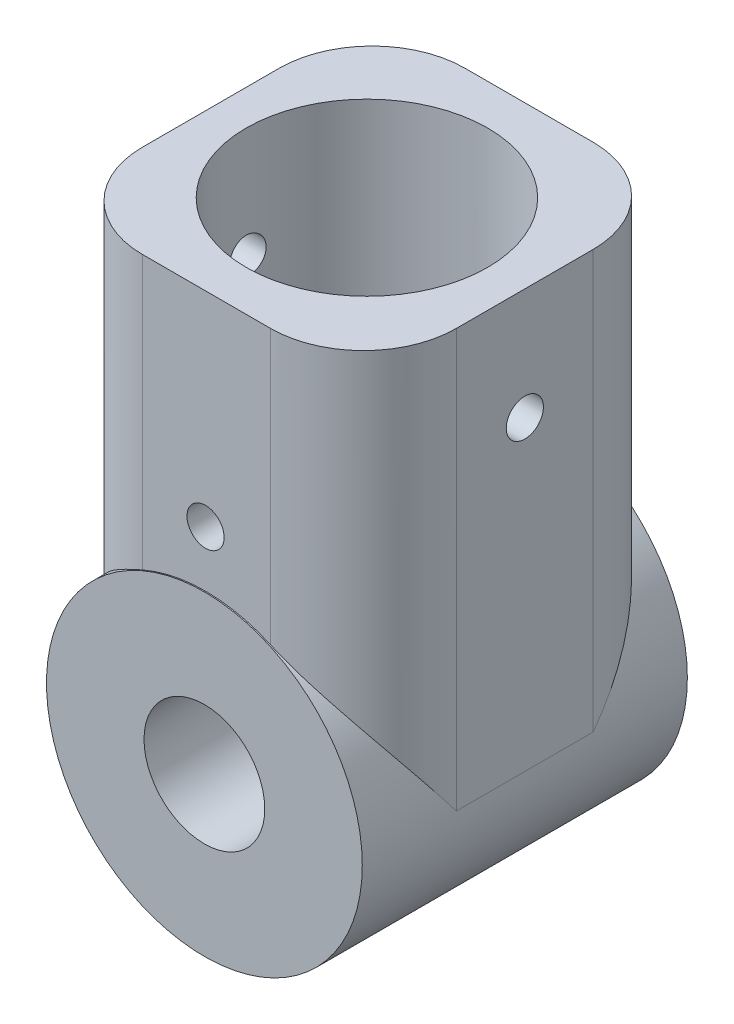
SolidWorks part; units mm, degrees
ref_plane "Спереди" through (0, 0, 0) normal (0, 0, 1) x (1, 0, 0)
ref_plane "Сверху" through (0, 0, 0) normal (0, 1, 0) x (1, 0, 0)
ref_plane "Справа" through (0, 0, 0) normal (1, 0, 0) x (0, 0, -1)
sketch "Эскиз1" plane through (0, 0, 0) normal (0, 0, 1) x (1, 0, 0)
  circle A0 centre (0, 0) radius 6.5
  circle A1 centre (0, 0) radius 17
extrude "Бобышка-Вытянуть2" add sketch "Эскиз1" along normal blind 35
ref_plane "Плоскость4" through (0, 45, 0) normal (0, 1, 0) x (1, 0, 0)
sketch "Эскиз3" plane through (0, 45, 0) normal (0, 1, 0) x (1, 0, 0)
  line L0 (17, -35) -> (17, 0) construction
  line L13 (-16.7953, -0.1471) -> (17, -0.1471)
  line L14 (-16.7953, -0.1471) -> (-16.7953, -34.8751)
  line L15 (-16.7953, -34.8751) -> (17, -34.8751)
  line L16 (17, -0.1471) -> (17, -34.8751)
  line L17 (-16.7953, -0.1471) -> (-17, 0) construction
  line L18 (-17, 0) -> (-17, -35) construction
  line L19 (-16.7953, -34.8751) -> (-17, -35) construction
  circle A1 centre (0, -17.5) radius 13
extrude "Бобышка-Вытянуть7" add sketch "Эскиз3" against normal blind 45
sketch "Эскиз4" plane through (0, 0, 0) normal (0, 0, -1) x (-1, 0, 0)
  circle A0 centre (0, 0) radius 6.5
extrude "Вырез-Вытянуть1" cut sketch "Эскиз4" against normal through all
sketch "Эскиз12" plane through (0, 0, 0) normal (0, 0, -1) x (-1, 0, 0)
  line L0 (0, 23) -> (0, 0) construction
  circle A3 centre (0, 23) radius 2
extrude "Вырез-Вытянуть11" cut sketch "Эскиз12" against normal blind 45
sketch "Эскиз15" plane through (-16.7953, 0, 0) normal (-1, 0, 0) x (0, 0, 1)
  line L0 (0, 0) -> (0, 33) construction
  line L1 (0, 33) -> (17.5, 33) construction
  circle A1 centre (17.5, 33) radius 2
extrude "Вырез-Вытянуть12" cut sketch "Эскиз15" against normal blind 45
fillet "Скругление4" radius 10 4 edges at (-16.7953, 23.8152, 0.1471) (17, 22.5, 0.1471) (17, 22.5, 34.8751) (-16.7953, 23.8152, 34.8751)
sketch "Эскиз20" plane through (0, 45, 0) normal (0, 1, 0) x (1, 0, 0)
  circle A3 centre (0, -17.5) radius 13
extrude "Вырез-Вытянуть18" cut sketch "Эскиз20" against normal blind 31
sketch "Эскиз25" plane through (0, 14, 0) normal (0, 1, 0) x (1, 0, 0)
  circle A2 centre (0, -17.5) radius 13
extrude "Бобышка-Вытянуть10" add sketch "Эскиз25" along normal blind 1
sketch3d "Трехмерный эскиз1"
  point P0 (-14.7779, 8.4033, 37.4657)
sketch "Эскиз26" plane through (0, 0, 0) normal (0, 0, -1) x (-1, 0, 0)
  circle A0 centre (0, 0) radius 6.5
  circle A1 centre (0, 0) radius 5.5
extrude "Бобышка-Вытянуть11" add sketch "Эскиз26" against normal blind 2
